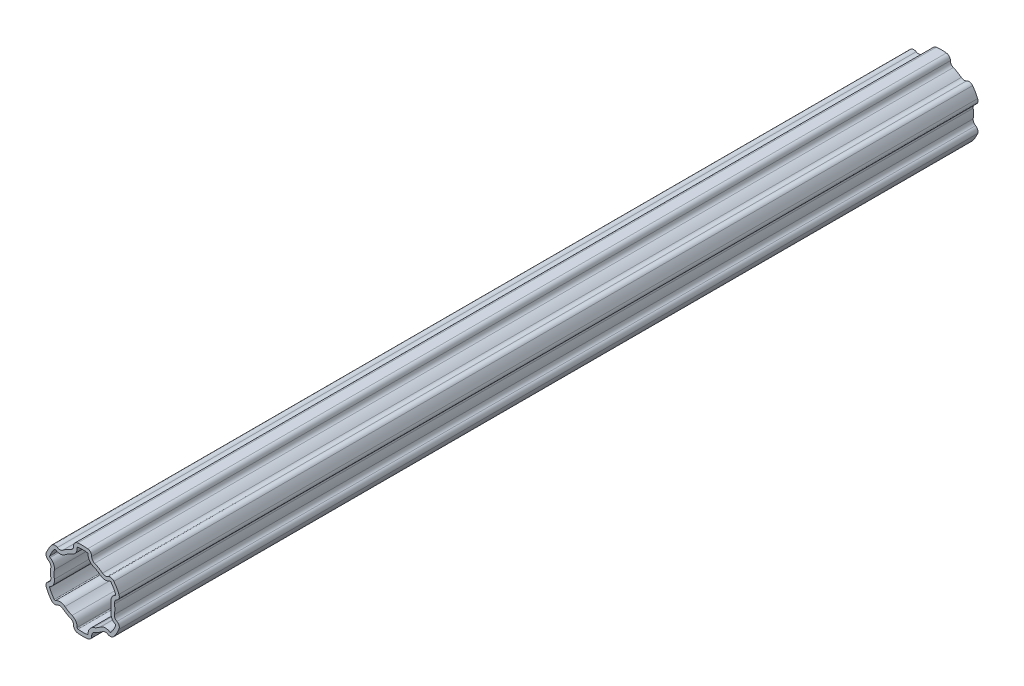
SolidWorks part; units mm, degrees
material "6061 Alloy"
ref_plane "Front Plane" through (0, 0, 0) normal (0, 0, 1) x (1, 0, 0)
ref_plane "Top Plane" through (0, 0, 0) normal (0, 1, 0) x (1, 0, 0)
ref_plane "Right Plane" through (0, 0, 0) normal (1, 0, 0) x (0, 0, -1)
sketch "Sketch1" plane through (0, 0, 0) normal (0, 0, 1) x (1, 0, 0)
  arc A0 (-4.7152, 11.7788) -> (-7.8431, 9.9729) centre (0, 0) ccw
  arc A1 (-12.0149, 9.7349) -> (-7.8431, 9.9729) centre (-10.0994, 12.842) ccw
  arc A2 (-12.0149, 9.7349) -> (-12.6087, 9.6249) centre (-12.251, 9.3519) ccw
  arc A3 (-12.6087, 9.6249) -> (-14.6398, 6.107) centre (0, 0) ccw
  arc A4 (-14.6398, 6.107) -> (-14.4381, 5.5377) centre (-14.2245, 5.9338) ccw
  arc A5 (-12.5583, 1.8059) -> (-14.4381, 5.5377) centre (-16.1712, 2.3254) ccw
  arc A6 (-12.5583, 1.8059) -> (-12.6875, 0) centre (0, 0) ccw
  arc A7 (-12.6875, 0) -> (-12.5583, -1.8059) centre (0, 0) ccw
  arc A8 (-14.4381, -5.5377) -> (-12.5583, -1.8059) centre (-16.1712, -2.3254) ccw
  arc A9 (-14.4381, -5.5377) -> (-14.6398, -6.107) centre (-14.2245, -5.9338) ccw
  arc A10 (-14.6398, -6.107) -> (-12.6087, -9.6249) centre (0, 0) ccw
  arc A11 (-12.6087, -9.6249) -> (-12.0149, -9.7349) centre (-12.251, -9.3519) ccw
  arc A12 (-7.8431, -9.9729) -> (-12.0149, -9.7349) centre (-10.0994, -12.842) ccw
  arc A13 (-7.8431, -9.9729) -> (-4.7152, -11.7788) centre (0, 0) ccw
  arc A14 (-2.4233, -15.2726) -> (-4.7152, -11.7788) centre (-6.0718, -15.1673) ccw
  arc A15 (-2.4233, -15.2726) -> (-2.0311, -15.7319) centre (-1.9735, -15.2856) ccw
  arc A16 (-2.0311, -15.7319) -> (2.0311, -15.7319) centre (0, 0) ccw
  arc A17 (2.0311, -15.7319) -> (2.4235, -15.2856) centre (1.9735, -15.2856) ccw
  arc A18 (2.4235, -15.2856) -> (2.4233, -15.2726) centre (1.9735, -15.2856) ccw
  arc A19 (2.4217, -15.1673) -> (2.4233, -15.2726) centre (6.0718, -15.1673) ccw
  arc A20 (4.7152, -11.7788) -> (2.4217, -15.1673) centre (6.0718, -15.1673) ccw
  arc A21 (4.7152, -11.7788) -> (7.8431, -9.9729) centre (0, 0) ccw
  arc A22 (12.0149, -9.7349) -> (7.8431, -9.9729) centre (10.0994, -12.842) ccw
  arc A23 (12.0149, -9.7349) -> (12.6087, -9.6249) centre (12.251, -9.3519) ccw
  arc A24 (12.6087, -9.6249) -> (14.6398, -6.107) centre (0, 0) ccw
  arc A25 (14.6398, -6.107) -> (14.6745, -5.9338) centre (14.2245, -5.9338) ccw
  arc A26 (14.6745, -5.9338) -> (14.4381, -5.5377) centre (14.2245, -5.9338) ccw
  arc A27 (12.5212, -2.3254) -> (14.4381, -5.5377) centre (16.1712, -2.3254) ccw
  arc A28 (12.5583, -1.8059) -> (12.5212, -2.3254) centre (16.1712, -2.3254) ccw
  arc A29 (12.5583, -1.8059) -> (12.5583, 1.8059) centre (0, 0) ccw
  arc A30 (12.5212, 2.3254) -> (12.5583, 1.8059) centre (16.1712, 2.3254) ccw
  arc A31 (14.4381, 5.5377) -> (12.5212, 2.3254) centre (16.1712, 2.3254) ccw
  arc A32 (14.4381, 5.5377) -> (14.6745, 5.9338) centre (14.2245, 5.9338) ccw
  arc A33 (14.6745, 5.9338) -> (14.6398, 6.107) centre (14.2245, 5.9338) ccw
  arc A34 (14.6398, 6.107) -> (12.6087, 9.6249) centre (0, 0) ccw
  arc A35 (12.6087, 9.6249) -> (12.0149, 9.7349) centre (12.251, 9.3519) ccw
  arc A36 (7.8431, 9.9729) -> (12.0149, 9.7349) centre (10.0994, 12.842) ccw
  arc A37 (7.8431, 9.9729) -> (4.7152, 11.7788) centre (0, 0) ccw
  arc A38 (2.4217, 15.1673) -> (4.7152, 11.7788) centre (6.0718, 15.1673) ccw
  arc A39 (2.4233, 15.2726) -> (2.4217, 15.1673) centre (6.0718, 15.1673) ccw
  arc A40 (2.4233, 15.2726) -> (2.4235, 15.2856) centre (1.9735, 15.2856) ccw
  arc A41 (2.4235, 15.2856) -> (2.0311, 15.7319) centre (1.9735, 15.2856) ccw
  arc A42 (2.0311, 15.7319) -> (-2.0311, 15.7319) centre (0, 0) ccw
  arc A43 (-2.0311, 15.7319) -> (-2.4233, 15.2726) centre (-1.9735, 15.2856) ccw
  arc A44 (-4.7152, 11.7788) -> (-2.4233, 15.2726) centre (-6.0718, 15.1673) ccw
  arc A45 (-5.3052, 13.2526) -> (-8.8244, 11.2207) centre (0, 0) ccw
  arc A46 (-11.1818, 11.0863) -> (-8.8244, 11.2207) centre (-10.0994, 12.842) ccw
  arc A47 (-11.1818, 11.0863) -> (-13.8706, 10.5882) centre (-12.251, 9.3519) ccw
  arc A48 (-13.8706, 10.5882) -> (-16.1049, 6.7182) centre (0, 0) ccw
  arc A49 (-16.1049, 6.7182) -> (-15.1919, 4.1406) centre (-14.2245, 5.9338) ccw
  arc A50 (-14.1297, 2.0318) -> (-15.1919, 4.1406) centre (-16.1712, 2.3254) ccw
  arc A51 (-14.1297, 2.0318) -> (-14.275, 0) centre (0, 0) ccw
  arc A52 (-14.275, 0) -> (-14.1297, -2.0318) centre (0, 0) ccw
  arc A53 (-15.1919, -4.1406) -> (-14.1297, -2.0318) centre (-16.1712, -2.3254) ccw
  arc A54 (-15.1919, -4.1406) -> (-16.1049, -6.7182) centre (-14.2245, -5.9338) ccw
  arc A55 (-16.1049, -6.7182) -> (-13.8706, -10.5882) centre (0, 0) ccw
  arc A56 (-13.8706, -10.5882) -> (-11.1818, -11.0863) centre (-12.251, -9.3519) ccw
  arc A57 (-8.8244, -11.2207) -> (-11.1818, -11.0863) centre (-10.0994, -12.842) ccw
  arc A58 (-8.8244, -11.2207) -> (-5.3052, -13.2526) centre (0, 0) ccw
  arc A59 (-4.0101, -15.2268) -> (-5.3052, -13.2526) centre (-6.0718, -15.1673) ccw
  arc A60 (-4.0101, -15.2268) -> (-2.2343, -17.3064) centre (-1.9735, -15.2856) ccw
  arc A61 (-2.2343, -17.3064) -> (2.2343, -17.3064) centre (0, 0) ccw
  arc A62 (2.2343, -17.3064) -> (4.011, -15.2856) centre (1.9735, -15.2856) ccw
  arc A63 (4.011, -15.2856) -> (4.0101, -15.2268) centre (1.9735, -15.2856) ccw
  arc A64 (4.0092, -15.1673) -> (4.0101, -15.2268) centre (6.0718, -15.1673) ccw
  arc A65 (5.3052, -13.2526) -> (4.0092, -15.1673) centre (6.0718, -15.1673) ccw
  arc A66 (5.3052, -13.2526) -> (8.8244, -11.2207) centre (0, 0) ccw
  arc A67 (11.1818, -11.0863) -> (8.8244, -11.2207) centre (10.0994, -12.842) ccw
  arc A68 (11.1818, -11.0863) -> (13.8706, -10.5882) centre (12.251, -9.3519) ccw
  arc A69 (13.8706, -10.5882) -> (16.1049, -6.7182) centre (0, 0) ccw
  arc A70 (16.1049, -6.7182) -> (16.262, -5.9338) centre (14.2245, -5.9338) ccw
  arc A71 (16.262, -5.9338) -> (15.1919, -4.1406) centre (14.2245, -5.9338) ccw
  arc A72 (14.1087, -2.3254) -> (15.1919, -4.1406) centre (16.1712, -2.3254) ccw
  arc A73 (14.1297, -2.0318) -> (14.1087, -2.3254) centre (16.1712, -2.3254) ccw
  arc A74 (14.1297, -2.0318) -> (14.1297, 2.0318) centre (0, 0) ccw
  arc A75 (14.1087, 2.3254) -> (14.1297, 2.0318) centre (16.1712, 2.3254) ccw
  arc A76 (15.1919, 4.1406) -> (14.1087, 2.3254) centre (16.1712, 2.3254) ccw
  arc A77 (15.1919, 4.1406) -> (16.262, 5.9338) centre (14.2245, 5.9338) ccw
  arc A78 (16.262, 5.9338) -> (16.1049, 6.7182) centre (14.2245, 5.9338) ccw
  arc A79 (16.1049, 6.7182) -> (13.8706, 10.5882) centre (0, 0) ccw
  arc A80 (13.8706, 10.5882) -> (11.1818, 11.0863) centre (12.251, 9.3519) ccw
  arc A81 (8.8244, 11.2207) -> (11.1818, 11.0863) centre (10.0994, 12.842) ccw
  arc A82 (8.8244, 11.2207) -> (5.3052, 13.2526) centre (0, 0) ccw
  arc A83 (4.0092, 15.1673) -> (5.3052, 13.2526) centre (6.0718, 15.1673) ccw
  arc A84 (4.0101, 15.2268) -> (4.0092, 15.1673) centre (6.0718, 15.1673) ccw
  arc A85 (4.0101, 15.2268) -> (4.011, 15.2856) centre (1.9735, 15.2856) ccw
  arc A86 (4.011, 15.2856) -> (2.2343, 17.3064) centre (1.9735, 15.2856) ccw
  arc A87 (2.2343, 17.3064) -> (-2.2343, 17.3064) centre (0, 0) ccw
  arc A88 (-2.2343, 17.3064) -> (-4.0101, 15.2268) centre (-1.9735, 15.2856) ccw
  arc A89 (-5.3052, 13.2526) -> (-4.0101, 15.2268) centre (-6.0718, 15.1673) ccw
extrude "Boss-Extrude1" add sketch "Sketch1" along normal blind 381
equation "\"Length\"= 15"
equation "\"D1@Boss-Extrude1\"=\"Length\""
